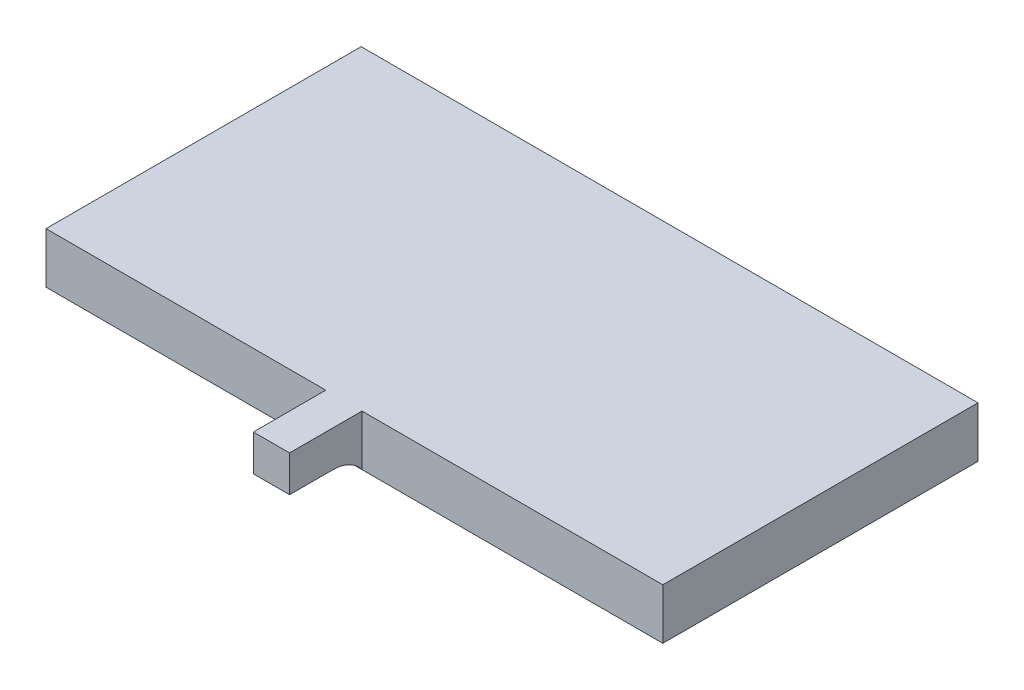
SolidWorks part; units mm, degrees
ref_plane "Front Plane" through (0, 0, 0) normal (0, 0, 1) x (1, 0, 0)
ref_plane "Top Plane" through (0, 0, 0) normal (0, 1, 0) x (1, 0, 0)
ref_plane "Right Plane" through (0, 0, 0) normal (1, 0, 0) x (0, 0, -1)
sketch "Sketch1" plane through (0, 0, 0) normal (0, 1, 0) x (1, 0, 0)
  line L1 (0, 0) -> (165, 0)
  line L2 (0, 0) -> (0, 82)
  line L3 (0, 82) -> (165, 82)
  line L4 (165, 0) -> (165, 82)
  line L5 (100, 2) -> (163, 2)
  line L6 (100, 2) -> (100, 80)
  line L7 (100, 80) -> (163, 80)
  line L8 (163, 2) -> (163, 80)
  line L9 (-2.7737, -2.5) -> (167.5, -2.5)
  line L10 (-2.7737, -2.5) -> (-2.7737, 84.5)
  line L11 (-2.7737, 84.5) -> (167.5, 84.5)
  line L12 (167.5, -2.5) -> (167.5, 84.5)
  point P13 (0, 0)
  point P14 (0, 0)
  dimension "D1" = 165
  dimension "D2" = 82
  dimension "D3" = 2
  dimension "D4" = 2
  dimension "D5" = 2
  dimension "D6" = 65
  dimension "D7" = 2.5
  dimension "D8" = 2.5
  dimension "D9" = 2.5
extrude "Boss-Extrude1" add sketch "Sketch1" along normal blind 2 contours L9 L12 L11 L10
extrude "Boss-Extrude5" add sketch "Sketch1<9>" along normal blind 2 separate body contours L9 L12 L11 L10
sketch "Sketch1<9>" plane through (0, 0, 0) normal (0, 1, 0) x (1, 0, 0) same geometry as "Sketch1"
extrude "Cut-Extrude3" cut sketch "Sketch1<10>" along normal blind 9 contours L6 L7 L8 L5
sketch "Sketch1<10>" plane through (0, 0, 0) normal (0, 1, 0) x (1, 0, 0) same geometry as "Sketch1"
extrude "Boss-Extrude6" add sketch "Sketch1<12>" along normal blind 14 contours L11 L12 L9 L10
sketch "Sketch1<12>" plane through (0, 0, 0) normal (0, 1, 0) x (1, 0, 0) same geometry as "Sketch1"
extrude "Cut-Extrude4" cut sketch "Sketch1<13>" along normal blind 10 contours L7 L8 L5 L6
sketch "Sketch1<13>" plane through (0, 0, 0) normal (0, 1, 0) x (1, 0, 0) same geometry as "Sketch1"
sketch "Sketch8" plane through (-2.7737, 0, 0) normal (-1, 0, 0) x (0, 0, 1)
  line L0 (2.5, 14) -> (-84.5, 14) construction
  line L1 (-82.6737, 13) -> (0.8523, 13)
  line L2 (-82.6737, 13) -> (-82.6737, 1.5)
  line L3 (-82.6737, 1.5) -> (0.8523, 1.5)
  line L4 (0.8523, 13) -> (0.8523, 1.5)
  line L5 (2.5, 0) -> (-84.5, 0) construction
  dimension "D1" = 1
  dimension "D2" = 1.5
extrude "Cut-Extrude5" cut sketch "Sketch8" against normal blind 168 contours L3 L4 L1 L2
sketch "Sketch9" plane through (0, 0, 2.5) normal (0, 0, 1) x (1, 0, 0)
  line L0 (-2.7737, 14) -> (167.5, 14) construction
  line L1 (74.4605, 14) -> (84.4605, 14)
  line L2 (74.4605, 14) -> (74.4605, 4)
  line L3 (74.4605, 4) -> (84.4605, 4)
  line L4 (84.4605, 14) -> (84.4605, 4)
  dimension "D1" = 10
  dimension "D2" = 10
delete or keep bodies "Body-Delete/Keep 2" type delete bodies bodies 101
extrude "Boss-Extrude8" add sketch "Sketch9" along normal blind 20
fillet "Fillet1" radius 10 1 edges at (79.4605, 4, 2.5)
ref_plane "Plane7" through (74.4605, 4, 10.5) normal (1, 0, 0) x (0, 0, -1)
ref_plane "Plane2" through (167.5, 2, 2.5) normal (1, 0, 0) x (0, 0, -1)
ref_plane "Plane3" through (-2.7737, 2, 2.5) normal (1, 0, 0) x (0, 0, -1)
